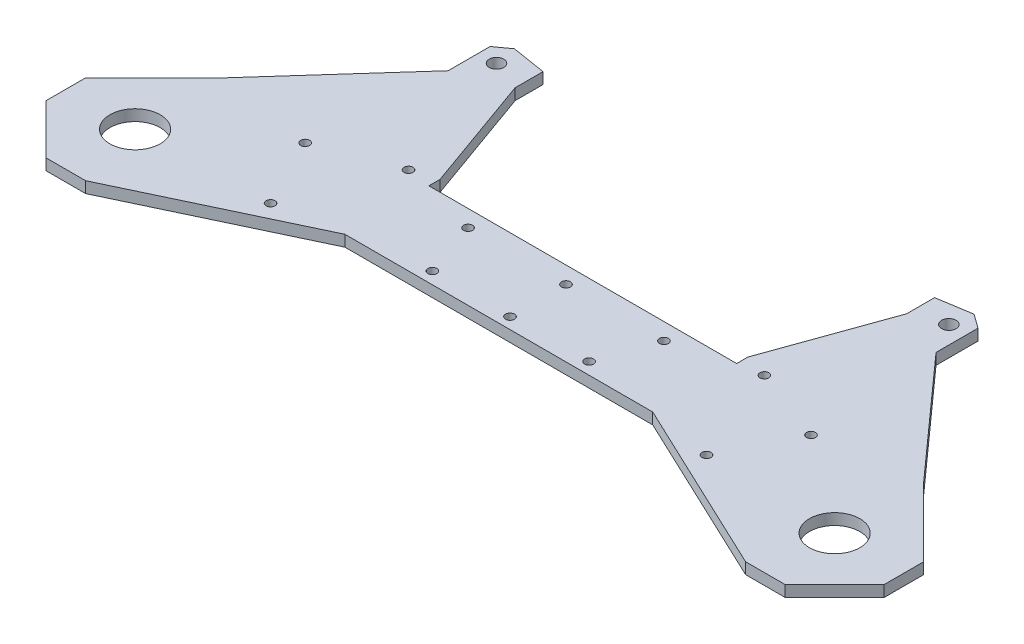
SolidWorks part; units mm, degrees
material "Thornel Mat VMA"
ref_plane "前视基准面" through (0, 0, 0) normal (0, 0, 1) x (1, 0, 0)
ref_plane "上视基准面" through (0, 0, 0) normal (0, 1, 0) x (1, 0, 0)
ref_plane "右视基准面" through (0, 0, 0) normal (1, 0, 0) x (0, 0, -1)
sketch "草图1" plane through (0, 0, 0) normal (0, 1, 0) x (1, 0, 0)
  line L0 (15.9099, 15.9099) -> (20, 20) construction
  line L1 (0, 31.8198) -> (-31.8198, 0)
  line L2 (-31.8198, 0) -> (0, -31.8198)
  line L3 (0, -31.8198) -> (31.8198, 0)
  line L4 (31.8198, 0) -> (0, 31.8198) construction
  line L5 (250, 31.8198) -> (218.1802, 0) construction
  line L6 (218.1802, 0) -> (250, -31.8198)
  line L7 (250, -31.8198) -> (281.8198, 0)
  line L8 (281.8198, 0) -> (250, 31.8198)
  line L9 (20, 20) -> (230, 20) construction
  line L10 (234.0901, 15.9099) -> (230, 20) construction
  line L11 (36.8198, 5) -> (213.1802, 5)
  line L12 (13.7868, 35) -> (230, 35)
  line L13 (31.8198, 0) -> (36.8198, 5)
  line L14 (244.6967, 26.5165) -> (236.2132, 35)
  line L15 (5.3033, 26.5165) -> (13.7868, 35)
  line L16 (218.1802, 0) -> (213.1802, 5)
  line L17 (244.6967, 26.5165) -> (240.6066, 30.6066) construction
  line L18 (5.3033, 26.5165) -> (9.3934, 30.6066) construction
  line L19 (20, 35) -> (230, 35) construction
  line L20 (230, 35) -> (236.2132, 35)
  line L22 (20, 5) -> (230, 5) construction
  line L24 (0, 31.8198) -> (5.3033, 26.5165)
  line L28 (244.6967, 26.5165) -> (250, 31.8198)
  circle A0 centre (0, 0) radius 9
  circle A1 centre (250, 0) radius 9
  circle A2 centre (0, 0) radius 22.5 construction
  circle A3 centre (250, 0) radius 22.5 construction
  point P23 (26.5165, 5.3033)
  point P24 (30.6066, 9.3934)
  point P29 (223.4835, 5.3033)
  point P30 (219.3934, 9.3934)
  dimension "D1" = 18
  dimension "D2" = 18
  dimension "D3" = 250
  dimension "D4" = 45
  dimension "D5" = 45
  dimension "D6" = 20
  dimension "D7" = 15
  dimension "D8" = 15
  dimension "D9" = 15
  dimension "D10" = 15
extrude "凸台-拉伸1" add sketch "草图1" along normal blind 4 contours L28 L14 L20 L12 L15 L24 L1 L2 L3 L11 L6 L7 L8 A1 A0 region at (125, 0, -13.2695)
fillet "圆角3" radius 50 2 edges at (236.2132, 2, -35) (13.7868, 2, -35)
chamfer "倒角1" distance 10 angle 45 4 edges at (281.8198, 2, 0) (250, 2, 31.8198) (0, 2, 31.8198) (-31.8198, 2, 0)
fillet "圆角4" radius 170 4 edges at (244.6967, 2, -26.5165) (5.3033, 2, -26.5165) (213.1802, 2, -5) (36.8198, 2, -5)
sketch "草图2" plane through (0, 4, 0) normal (0, 1, 0) x (1, 0, 0)
  line L0 (33.1669, 35) -> (44.1669, 35) construction
  line L1 (33.1669, 35) -> (216.8331, 35) construction
  line L2 (44.1669, 35) -> (44.1669, 85) construction
  line L3 (205.8331, 35) -> (205.8331, 85) construction
  line L4 (33.1669, 35) -> (70, 35)
  line L5 (125, 35) -> (125, -28.1037) construction
  line L6 (125, 35) -> (70, 35) construction
  line L7 (125, 35) -> (180, 35) construction
  line L8 (70, 35) -> (70, 89.938)
  line L9 (70, 89.938) -> (52.1738, 89.9808)
  line L10 (216.8331, 35) -> (205.8331, 35) construction
  line L11 (180, 89.938) -> (197.8262, 89.9808)
  line L12 (180, 35) -> (180, 89.938)
  line L13 (216.8331, 35) -> (180, 35)
  line L14 (41.2397, 89.0536) -> (37.1861, 86.1264)
  line L15 (41.2397, 89.0536) -> (45.2933, 91.9808)
  line L16 (212.8139, 86.1264) -> (215.0658, 75.8033)
  line L17 (208.7603, 89.0536) -> (212.8139, 86.1264)
  line L19 (45.2933, 91.9808) -> (52.1738, 89.9808)
  line L20 (37.1861, 86.1264) -> (34.9342, 75.8033)
  line L21 (208.7603, 89.0536) -> (204.7067, 91.9808)
  line L22 (204.7067, 91.9808) -> (197.8262, 89.9808)
  line L24 (34.9342, 75.8033) -> (0, 31.8198)
  line L25 (215.0658, 75.8033) -> (250, 31.8198)
  circle A0 centre (44.1669, 85) radius 2.6
  arc A2 (0, 31.8198) -> (24.6197, 34.264) centre (-4.4406, 201.7618) ccw construction
  arc A3 (33.1669, 35) -> (24.6197, 34.264) centre (33.1669, -15) ccw construction
  arc A4 (0, 31.8198) -> (24.6197, 34.264) centre (-4.4406, 201.7618) ccw
  arc A5 (33.1669, 35) -> (24.6197, 34.264) centre (33.1669, -15) ccw
  arc A6 (216.8331, 35) -> (225.3803, 34.264) centre (216.8331, -15) cw
  arc A7 (250, 31.8198) -> (225.3803, 34.264) centre (254.4406, 201.7618) cw
  circle A9 centre (205.8331, 85) radius 2.6
  arc M8 (250, 31.8198) -> (225.3803, 34.264) centre (254.4406, 201.7618) cw
  arc M9 (225.3803, 34.264) -> (216.8331, 35) centre (216.8331, -15) ccw
  line M10 (216.8331, 35) -> (33.1669, 35)
  arc M11 (33.1669, 35) -> (24.6197, 34.264) centre (33.1669, -15) ccw
  arc M12 (24.6197, 34.264) -> (0, 31.8198) centre (-4.4406, 201.7618) cw
  dimension "D3" = 5.2
  dimension "D1" = 11
  dimension "D2" = 50
  dimension "D5" = 55
extrude "凸台-拉伸2" add sketch "草图2" against normal blind 4 contours L24 L8 L9 A0 M12 M11 M10 | L11 L12 A9 M8 M10 M9 region at (44.6422, 4, -58.003) region at (205.3578, 4, -58.003)
chamfer "倒角2" distance 10 angle 45 2 edges at (180, 2, -89.938) (70, 2, -89.938) first distance on face at (180, 2, -62.469) first distance on face at (61.0869, 2, -89.9594)
fillet "圆角6" radius 5 3 edges at (34.9342, 2, -75.8033) (52.1738, 2, -89.9808) (197.8262, 2, -89.9808)
sketch "草图6" plane through (0, 4, 0) normal (0, 1, 0) x (1, 0, 0)
  line L0 (37.1861, 86.1264) -> (37.8249, 89.0546)
  line L1 (45.2933, 91.9808) -> (42.8575, 92.6888)
  line L2 (37.1861, 86.1264) -> (45.2933, 91.9808)
  line L3 (125, 35) -> (125, 98.4303) construction
  line L4 (36.0153, 87.7479) -> (44.1224, 93.6022)
  line L5 (37.8249, 89.0546) -> (42.8575, 92.6888)
  line L6 (70, 35) -> (180, 35) construction
  line L7 (212.1751, 89.0546) -> (207.1425, 92.6888)
  line L8 (212.8139, 86.1264) -> (204.7067, 91.9808)
  line L9 (204.7067, 91.9808) -> (207.1425, 92.6888)
  line L10 (212.8139, 86.1264) -> (212.1751, 89.0546)
  dimension "D1" = 2
extrude "凸台-拉伸4" add sketch "草图6" against normal blind 4
sketch "草图7" plane through (0, 4, 0) normal (0, 1, 0) x (1, 0, 0)
  line L0 (125, 35) -> (125, 5) construction
  line L1 (70, 35) -> (180, 35) construction
  line L2 (103.1418, 5) -> (146.8582, 5) construction
  circle A0 centre (34.6096, 26.1728) radius 1.6
  circle A1 centre (47.1137, 1.3128) radius 1.6
  circle A2 centre (97, 9.2557) radius 1.6
  circle A3 centre (125, 29) radius 1.6
  circle A4 centre (125, 9) radius 1.6
  circle A5 centre (61.4166, 36.3097) radius 1.6
  circle A6 centre (188.5834, 36.3097) radius 1.6
  circle A7 centre (153, 9.2557) radius 1.6
  circle A8 centre (202.8863, 1.3128) radius 1.6
  circle A9 centre (215.3904, 26.1728) radius 1.6
  circle A10 centre (90, 29) radius 1.6
  circle A11 centre (160, 29) radius 1.6
  dimension "D1" = 35
  dimension "D2" = 28
  dimension "D3" = 20
  dimension "D4" = 6
extrude "切除-拉伸3" cut sketch "草图7" against normal blind 10
sketch "草图8" plane through (0, 4, 0) normal (0, 1, 0) x (1, 0, 0)
  line L0 (125, 35) -> (125, 29)
  line L1 (212.1751, 89.0546) -> (212.1751, 74.0546)
  line L2 (212.1751, 74.0546) -> (250, 31.8198)
  line L3 (70, 35) -> (180, 35) construction
  line L4 (125, 29) -> (90, 29)
  line L5 (125, 29) -> (160, 29)
  line L6 (125, 29) -> (125, 9)
  line L7 (125, 9) -> (153, 9.2557)
  line L8 (125, 9) -> (97, 9.2557)
  line L9 (37.8249, 89.0546) -> (37.8249, 74.0546)
  line L10 (37.8249, 74.0546) -> (0, 31.8198)
  line L11 (37.8249, 89.0546) -> (0, 89.0546)
  line L12 (0, 89.0546) -> (0, 31.8198)
  line L13 (212.1751, 89.0546) -> (250, 89.0546)
  line L14 (250, 89.0546) -> (250, 31.8198)
  line M29 (37.8249, 89.0546) -> (35.1817, 76.938)
  arc M30 (35.1817, 76.938) -> (34.2119, 74.8939) centre (30.2966, 78.0037) cw
  line M31 (34.2119, 74.8939) -> (0, 31.8198)
  line M45 (250, 31.8198) -> (215.0658, 75.8033)
  line M47 (215.0658, 75.8033) -> (212.1751, 89.0546)
  dimension "D1" = 15
  dimension "D2" = 15
extrude "切除-拉伸4" cut sketch "草图8" against normal blind 10 contours L11 L12 M31 M30 M29 | L10 L9 M29 M30 M31 | L1 L2 M45 M47 | L14 L13 M47 M45 region at (223.3863, 4, -64.1313) region at (235.8281, 4, -69.3833) region at (14.1702, 4, -69.3827) region at (26.6208, 4, -64.1415)
sketch "草图10" plane through (0, 4, 0) normal (0, 1, 0) x (1, 0, 0)
  line L0 (60, 89.962) -> (70, 39)
  line L1 (70, 35) -> (70, 79.914) construction
  line L2 (190.024, 89.9621) -> (180, 39)
  line L3 (180, 35) -> (180, 79.938) construction
  line L4 (60, 89.962) -> (70, 79.914)
  line L5 (70, 79.914) -> (70, 39)
  line L6 (190.024, 89.9621) -> (180, 79.938)
  line L7 (180, 79.938) -> (180, 39)
  dimension "D1" = 4
  dimension "D2" = 4
extrude "切除-拉伸5" cut sketch "草图10" against normal blind 10 contours L5 L0 L4 | L7 L2 L6
sketch "草图11" plane through (0, 4, 0) normal (0, 1, 0) x (1, 0, 0)
  line L0 (42.8575, 92.6888) -> (60, 89.962)
  line L1 (42.8575, 92.6888) -> (60.9482, 85.13)
  line L2 (60, 89.962) -> (70, 39) construction
  line L3 (60.9482, 85.13) -> (60, 89.962)
  line L4 (190.024, 89.9621) -> (207.1425, 92.6888)
  line L5 (207.1425, 92.6888) -> (188.8755, 84.1228)
  line L6 (190.024, 89.9621) -> (180, 39) construction
  line L7 (188.8755, 84.1228) -> (190.024, 89.9621)
extrude "凸台-拉伸6" add sketch "草图11" against normal blind 4
sketch "草图12" plane through (0, 4, 0) normal (0, 1, 0) x (1, 0, 0)
  line L0 (103.1418, 5) -> (27.7755, 5)
  line L1 (27.7755, 5) -> (224.8504, 5)
  line L2 (7.0711, -24.7487) -> (70, 5)
  line L3 (242.9289, -24.7487) -> (180, 5)
  line L4 (125, 29) -> (125, -3.3236)
  line L5 (7.0711, -24.7487) -> (4.8359, -20.0206)
  line L6 (4.8359, -20.0206) -> (68.8824, 7.3641)
  line L7 (68.8824, 7.3641) -> (183.2415, 7.3641)
  line L8 (183.2415, 7.3641) -> (242.9289, -20.0206)
  line L9 (242.9289, -20.0206) -> (242.9289, -24.7487)
  arc M17 (7.0711, -24.7487) -> (103.1418, 5) centre (103.1418, -165) cw
  arc M19 (146.8582, 5) -> (242.9289, -24.7487) centre (146.8582, -165) cw
  dimension "D1" = 110
  dimension "D2" = 55
extrude "凸台-拉伸7" add sketch "草图12" against normal blind 4 contours L2 M17 | L3 M19 | L9 L8 L1 L3 M19 | L6 L5 L2 L1 M17 region at (34.0655, 4, 9.1955) region at (31.0358, 4, 12.4707) region at (212.4547, 4, 7.7073) region at (218.9642, 4, 12.4707)
sketch "草图13" plane through (0, 4, 0) normal (0, 1, 0) x (1, 0, 0)
  line L0 (103.1418, 5) -> (190.2419, 5)
  line L1 (190.2419, 5) -> (51.2685, 5)
  line L2 (7.0711, -24.7487) -> (55.7339, -1.7441)
  line L3 (55.7339, -1.7441) -> (83.7099, 11.4812)
  line L4 (242.9289, -24.7487) -> (194.2661, -1.7441)
  line L5 (194.2661, -1.7441) -> (180, 5)
  line L6 (180, 5) -> (194.2661, -1.7441)
  line L7 (55.7339, -1.7441) -> (194.2661, -1.7441)
  arc M2 (55.7339, -1.7441) -> (103.1418, 5) centre (103.1418, -165) cw
  line M3 (103.1418, 5) -> (146.8582, 5)
  arc M4 (146.8582, 5) -> (194.2661, -1.7441) centre (146.8582, -165) cw
extrude "切除-拉伸6" cut sketch "草图13" against normal blind 4 contours L3 L1 M2 | L7 M2 M4 M3 | L5 L0 M4 region at (73.4247, 4, -3.1775) region at (125, 4, -1.2314) region at (176.5753, 4, -3.1775)
sketch "草图14" plane through (0, 4, 0) normal (0, 1, 0) x (1, 0, 0)
  line L0 (55.0621, 90.7475) -> (55.0621, 80.7475)
  line L1 (60, 89.962) -> (42.8575, 92.6888) construction
  line L2 (55.0621, 80.7475) -> (70, 39)
  line L3 (194.9618, 90.7486) -> (194.9618, 80.7486)
  line L4 (207.1425, 92.6888) -> (190.024, 89.9621) construction
  line L5 (194.9618, 80.7486) -> (180, 39)
  line L6 (55.0621, 90.7475) -> (60, 89.962)
  line L7 (60, 89.962) -> (70, 39)
  line L8 (194.9618, 90.7486) -> (190.024, 89.9621)
  line L9 (190.024, 89.9621) -> (180, 39)
  dimension "D1" = 10
  dimension "D2" = 10
  dimension "D3" = 5
  dimension "D4" = 5
extrude "切除-拉伸7" cut sketch "草图14" against normal blind 10 contours L7 L2 L0 L6 | L9 L5 L3 L8
